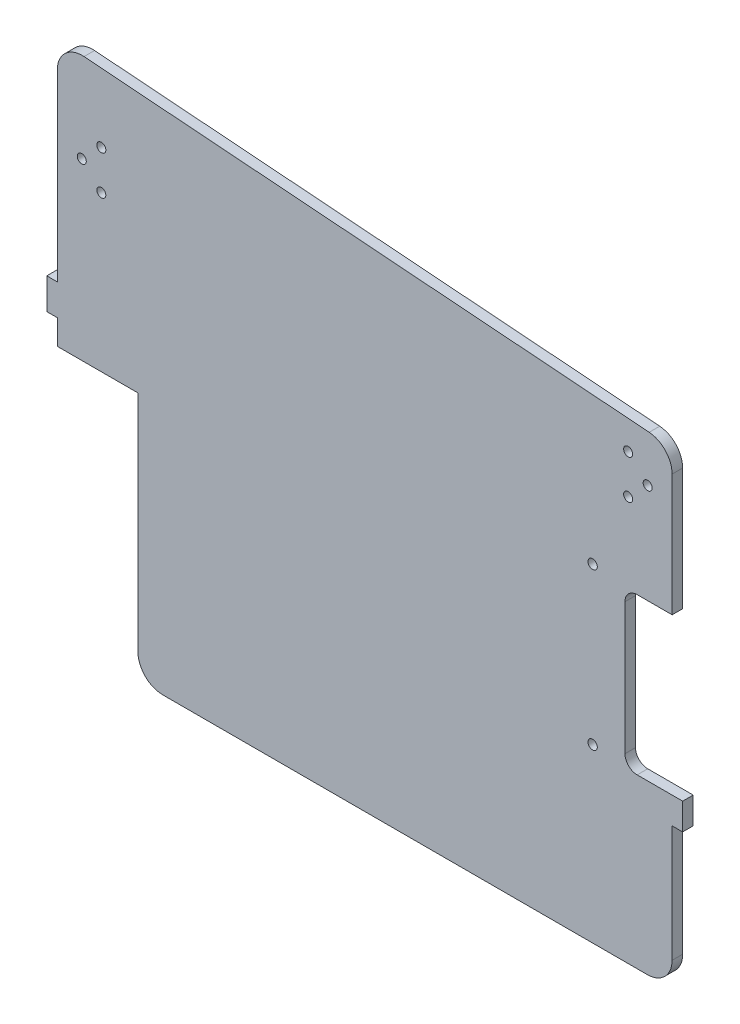
SolidWorks part; units mm, degrees
material "Acrylic (Medium-high impact)"
ref_plane "Front" through (0, 0, 0) normal (0, 0, 1) x (1, 0, 0)
ref_plane "Top" through (0, 0, 0) normal (0, 1, 0) x (1, 0, 0)
ref_plane "Right" through (0, 0, 0) normal (1, 0, 0) x (0, 0, -1)
ref_axis "side-side" through (80.9, 0, 0) along (-1, 0, 0)
ref_axis "up-down" through (0, 50, 0) along (0, -1, 0)
ref_axis "front-back" through (0, 0, -80.9) along (0, 0, 1)
sketch "Sketch2" plane through (0, 0, 0) normal (0, 0, 1) x (1, 0, 0)
  line L4 (68.795, -53.5865) -> (68.795, -125.5865)
  line L5 (68.795, -125.5865) -> (81.495, -125.5865)
  line L6 (81.495, -125.5865) -> (81.495, -53.5865)
  line L7 (81.495, -53.5865) -> (68.795, -53.5865)
  line L8 (68.795, -53.5865) -> (68.795, -125.5865)
  line L9 (68.795, -125.5865) -> (81.495, -125.5865)
  line L10 (81.495, -125.5865) -> (81.495, -53.5865)
  line L11 (81.495, -53.5865) -> (68.795, -53.5865)
  circle A1 centre (75.145, -57.5865) radius 1.2802
  circle A2 centre (75.145, -57.5865) radius 1.2802
  circle A3 centre (75.145, -121.5865) radius 1.2802
  circle A4 centre (75.145, -121.5865) radius 1.2802
  dimension "D1" = 0
  dimension "D2" = 0
  dimension "D3" = 0
sketch "Sketch3" plane through (0, 0, 0) normal (1, 0, 0) x (0, 0, -1)
  line L1 (0, 0) -> (0, -191.9523)
  line L3 (4.318, -191.9523) -> (4.318, 0)
  dimension "D1" = 4.318
sketch3d "3DSketch1"
  line L1 (-112, -157.0582, 90.6449) -> (-112, -155.4001, 91.7633)
  line L3 (-112, -180.2712, 74.9875) -> (-112, -181.9293, 73.8692)
  line L16 (-144, -158.8707, 92.4379) -> (-144, -181.2547, 77.3397)
  line L17 (-141.5, -183.3273, 75.9417) -> (-114.5, -183.3273, 75.9417)
  line L18 (-114.5, -183.3273, 75.9417) -> (-114.5, -181.6692, 77.0601)
  line L19 (-114.5, -181.6692, 77.0601) -> (-142, -181.6692, 77.0601)
  line L20 (-142, -181.6692, 77.0601) -> (-142, -158.4562, 92.7175)
  line L21 (-142, -158.4562, 92.7175) -> (-114.5, -158.4562, 92.7175)
  line L22 (-114.5, -158.4562, 92.7175) -> (-114.5, -156.7981, 93.8359)
  line L23 (-114.5, -156.7981, 93.8359) -> (-141.5, -156.7981, 93.8359)
  line L28 (-144, -192.8976, 90.1302) -> (-144, -61.7581, 178.5849)
  line L29 (-144, -61.7581, 178.5849) -> (-148.7625, -61.7581, 178.5849)
  line L30 (-148.7625, -61.7581, 178.5849) -> (-148.7625, -192.8976, 90.1302)
  line L31 (-148.7625, -192.8976, 90.1302) -> (-144, -192.8976, 90.1302)
  line L36 (107.682, -15.782, 126.7929) -> (107.682, -139.6668, 123.6948)
  line L37 (107.682, -139.6668, 123.6948) -> (112, -139.6668, 123.6948)
  line L38 (112, -139.6668, 123.6948) -> (112, -15.782, 126.7929)
  line L39 (112, -15.782, 126.7929) -> (107.682, -15.782, 126.7929)
  arc A4 (-141.5, -156.7981, 93.8359) -> (-144, -158.8707, 92.4379) centre (-141.5, -158.8707, 92.4379) ccw
  arc A5 (-144, -181.2547, 77.3397) -> (-141.5, -183.3273, 75.9417) centre (-141.5, -181.2547, 77.3397) ccw
  point P18 (-141.5, -160.2687, 94.5105)
  point P19 (-141.5, -182.6527, 79.4123)
sketch "Sketch4" plane through (0, 0, 0) normal (1, 0, 0) x (0, 0, -1)
  line L0 (4.318, -191.9523) -> (4.318, 0) construction
  line L1 (0, 0) -> (0, -191.9523) construction
  line L2 (4.318, -191.9523) -> (4.318, 0)
  line L3 (0, 0) -> (0, -191.9523)
  line L4 (0, 0) -> (4.318, 0)
  line L5 (0, -191.9523) -> (4.318, -191.9523)
  dimension "D1" = 4.318
extrude "Boss-Extrude1" add sketch "Sketch4" along normal up to vertex (107.682 mm away) and the other way up to vertex (144 mm away) up to point (107.682, -139.6668, 123.6948) other way up to point (-144, -61.7581, 178.5849)
sketch "Sketch5" plane through (0, 0, 0) normal (0, 0, 1) x (1, 0, 0)
  circle A0 centre (75.145, -57.5865) radius 1.905
  circle A1 centre (75.145, -121.5865) radius 1.905
  dimension "D1" = 3.81
extrude "Cut-Extrude1" cut sketch "Sketch5" against normal through all
sketch "Sketch6" plane through (-144, 0, 0) normal (-1, 0, 0) x (0, 0, 1)
  line L0 (0, 0) -> (0, -191.9523) construction
  line L1 (-4.318, -191.9523) -> (0, -191.9523)
  line L2 (-4.318, -191.9523) -> (-4.318, -89.9797)
  line L3 (-4.318, -89.9797) -> (0, -89.9797)
  line L4 (0, -191.9523) -> (0, -89.9797)
  line L5 (90.5798, -153.9891) -> (-26.1045, -75.2845) construction
  line L6 (92.4379, -158.8707) -> (77.3397, -181.2547) construction
  dimension "D1" = 0.508
extrude "Cut-Extrude2" cut sketch "Sketch6" against normal blind 33
sketch "Sketch7" plane through (0, 0, 0) normal (0, 0, 1) x (1, 0, 0)
  line L1 (107.682, 0) -> (-144, 0)
  line L3 (107.682, 0) -> (-144, 19.05)
  line L4 (-144, 0) -> (-144, 19.05)
  dimension "D1" = 19.05
extrude "Boss-Extrude2" add sketch "Sketch7" against normal up to surface (4.318 mm away) up to face at (77.05, -121.5865, -4.318)
sketch "Sketch8" plane through (0, 0, 0) normal (0, 0, 1) x (1, 0, 0)
  line L0 (107.682, 0) -> (107.682, -191.9523) construction
  line L1 (107.682, -59.3119) -> (93.378, -59.3119)
  line L2 (107.682, -59.3119) -> (107.682, -123.2067)
  line L3 (107.682, -123.2067) -> (93.378, -123.2067)
  line L4 (88.378, -64.3119) -> (88.378, -118.2067)
  circle A0 centre (75.145, -57.5865) radius 1.85 construction
  circle A1 centre (75.145, -57.5865) radius 1.85
  circle A2 centre (75.145, -121.5865) radius 1.85 construction
  circle A3 centre (75.145, -121.5865) radius 1.85
  arc A4 (93.378, -123.2067) -> (88.378, -118.2067) centre (93.378, -118.2067) cw
  arc A5 (93.378, -59.3119) -> (88.378, -64.3119) centre (93.378, -64.3119) ccw
  circle A6 centre (89.682, -10.45) radius 1.85 construction
  circle A7 centre (97.682, -18.45) radius 1.85 construction
  circle A8 centre (89.682, -26.45) radius 1.85 construction
  circle A9 centre (89.682, -10.45) radius 1.85
  circle A10 centre (97.682, -18.45) radius 1.85
  circle A11 centre (89.682, -26.45) radius 1.85
  circle A12 centre (-126, -26.45) radius 1.85 construction
  circle A13 centre (-126, -10.45) radius 1.85 construction
  circle A14 centre (-134, -18.45) radius 1.85 construction
  circle A15 centre (-126, -26.45) radius 1.85
  circle A16 centre (-126, -10.45) radius 1.85
  circle A17 centre (-134, -18.45) radius 1.85
  point P15 (88.378, -123.2067)
  dimension "D2" = 5
  dimension "D1" = 19.304
extrude "Cut-Extrude3" cut sketch "Sketch8" against normal blind 5.08
sketch "Sketch9" plane through (0, 0, 0) normal (0, 0, 1) x (1, 0, 0)
  line L0 (-144, 19.05) -> (-144, -89.9797) construction
  line L1 (107.682, -123.2067) -> (112, -123.2067)
  line L2 (107.682, -123.2067) -> (107.682, -134.1287)
  line L3 (107.682, -134.1287) -> (112, -134.1287)
  line L4 (112, -123.2067) -> (112, -134.1287)
  line L5 (-144, -67.1197) -> (-148.318, -67.1197)
  line L6 (-144, -67.1197) -> (-144, -79.8197)
  line L7 (-144, -79.8197) -> (-148.318, -79.8197)
  line L8 (-148.318, -67.1197) -> (-148.318, -79.8197)
  line L9 (-111, -89.9797) -> (-144, -89.9797) construction
  dimension "D1" = 4.318
  dimension "D2" = 10.922
  dimension "D3" = 12.7
  dimension "D4" = 4.318
  dimension "D5" = 10.16
extrude "Boss-Extrude3" add sketch "Sketch9" against normal up to surface (4.318 mm away) up to face at (-134, -20.3, -4.318)
fillet "Fillet2" radius 10.16 4 edges at (-111, -191.9523, -2.159) (-144, 19.05, -2.159) (107.682, 0, -2.159) (107.682, -191.9523, -2.159)
